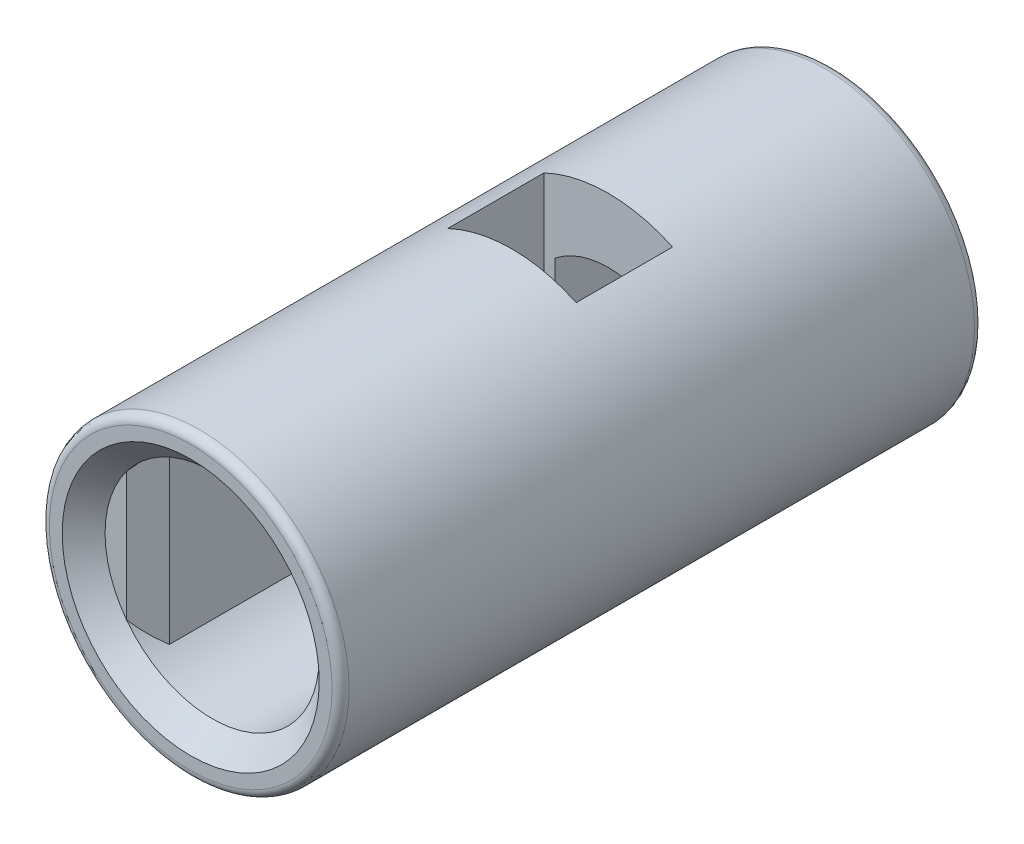
SolidWorks part; units mm, degrees
ref_plane "前视基准面" through (0, 0, 0) normal (0, 0, 1) x (1, 0, 0)
ref_plane "上视基准面" through (0, 0, 0) normal (0, 1, 0) x (1, 0, 0)
ref_plane "右视基准面" through (0, 0, 0) normal (1, 0, 0) x (0, 0, -1)
sketch "草图1" plane through (0, 0, 0) normal (0, 0, 1) x (1, 0, 0)
  line L2 (-1.25, 1.5612) -> (-1.25, -1.5612)
  line L4 (1.25, 1.5612) -> (1.25, -1.5612)
  arc A0 (1.25, 1.5612) -> (-1.25, 1.5612) centre (0, 0) ccw
  circle A1 centre (0, 0) radius 3.5
  arc A2 (-1.25, -1.5612) -> (1.25, -1.5612) centre (0, 0) ccw
extrude "凸台-拉伸1" add sketch "草图1" against normal blind 7.5 and the other way blind 7.5
sketch "草图2" plane through (0, 0, 0) normal (0, 1, 0) x (1, 0, 0)
  line L0 (0, 0) -> (-1.5, 0)
  line L1 (-1.5, 2.25) -> (1.5, 2.25)
  line L2 (-1.5, 2.25) -> (-1.5, 0)
  line L4 (1.5, 2.25) -> (1.5, 0)
  line L5 (0, 0) -> (1.5, 0)
  dimension "D1" = 2.25
  dimension "D2" = 1.5
  dimension "D3" = 1.5
extrude "切除-拉伸1" cut sketch "草图2" against normal up to next and the other way up to next
fillet "圆角1" radius 0.2 2 edges at (3.5, 0, -7.5) (3.5, 0, 7.5)
sketch "草图3" plane through (0, 0, 7.5) normal (0, 0, 1) x (1, 0, 0)
  circle A0 centre (0, 0) radius 2.5
  dimension "D1" = 5
extrude "切除-拉伸2" cut sketch "草图3" against normal blind 0.5
sketch "草图4" plane through (0, 0, 7) normal (0, 0, 1) x (1, 0, 0)
  line L0 (0, 0) -> (-1.5, 0) construction
  line L1 (-1.5, 0) -> (-1.5, 2)
  line L2 (-1.5, 0) -> (-1.5, -2)
  arc A0 (-1.5, -2) -> (-1.5, 2) centre (0, 0) ccw
  dimension "D1" = 5
  dimension "D2" = 1.5
extrude "切除-拉伸3" cut sketch "草图4" against normal blind 7
chamfer "倒角1" distance 0.5 angle 45 2 edges at (2.5, 0, 7.5) (-1.5, 0, 7)
chamfer "倒角2" distance 0.5 angle 45 4 edges at (0, 2, -7.5) (-1.25, 0, -7.5) (0, -2, -7.5) (1.25, 0, -7.5)
